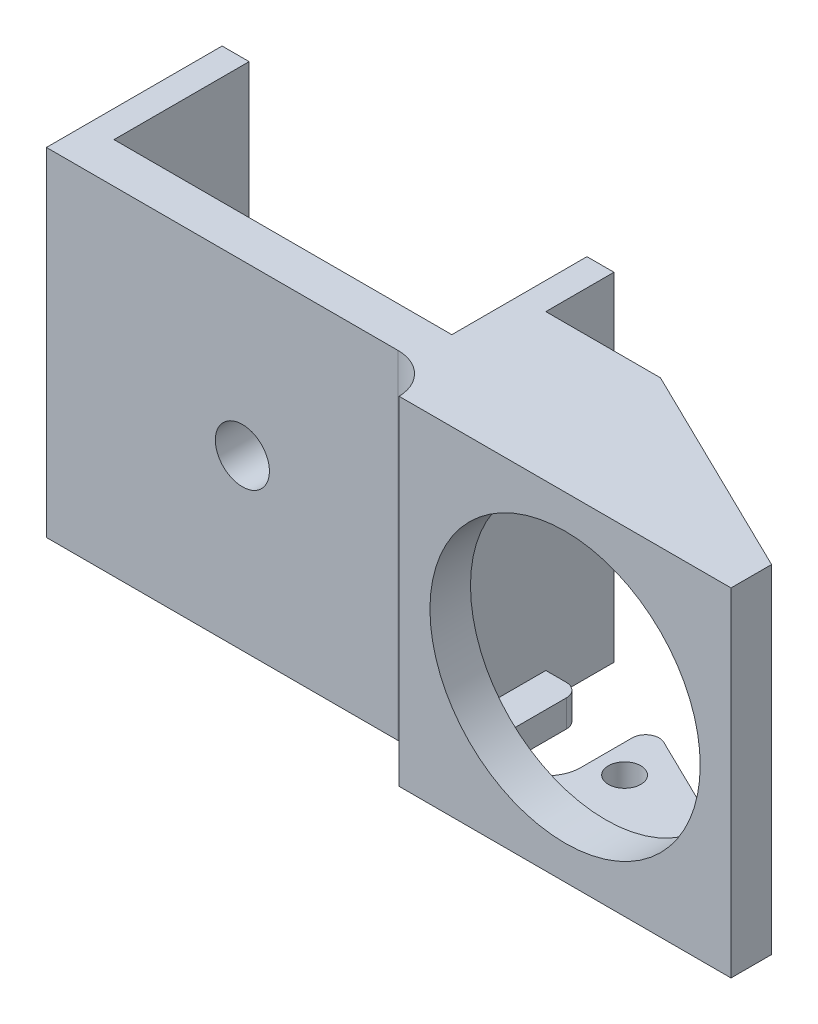
SolidWorks part; units mm, degrees
ref_plane "Front" through (0, 0, 0) normal (0, 0, 1) x (1, 0, 0)
ref_plane "Top" through (0, 0, 0) normal (0, 1, 0) x (1, 0, 0)
ref_plane "Right" through (0, 0, 0) normal (1, 0, 0) x (0, 0, -1)
sketch "Эскиз1" plane through (0, 0, 0) normal (0, 0, 1) x (1, 0, 0)
  line L1 (-12.2807, 12.5) -> (12.2807, 12.5)
  line L2 (-12.2807, 12.5) -> (-12.2807, -12.5)
  line L3 (-12.2807, -12.5) -> (12.2807, -12.5)
  line L4 (12.2807, 12.5) -> (12.2807, -12.5)
  line L5 (-12.2807, 12.5) -> (12.2807, -12.5) construction
  line L6 (-12.2807, -12.5) -> (12.2807, 12.5) construction
  circle A0 centre (0, 0) radius 10
  dimension "D1" = 25
  dimension "D2" = 20
extrude "Бобышка-Вытянуть1" add sketch "Эскиз1" along normal blind 3
sketch "Эскиз2" plane through (0, 0, 3) normal (0, 0, 1) x (1, 0, 0)
  line L0 (-12.2807, 12.5) -> (-41.2807, 12.5)
  line L1 (-41.2807, 12.5) -> (-41.2807, -12.5)
  line L2 (-41.2807, -12.5) -> (-12.2807, -12.5)
  line L3 (-12.2807, 12.5) -> (-12.2807, -12.5)
  dimension "D1" = 29
extrude "Бобышка-Вытянуть2" add sketch "Эскиз2" against normal blind 3 from offset 2.9 offset against normal yes
sketch "Эскиз4" plane through (0, 0, -2.9) normal (0, 0, -1) x (-1, 0, 0)
  line L0 (41.2807, -12.5) -> (12.2807, -12.5) construction
  line L1 (12.2807, 12.5) -> (14.2807, 12.5)
  line L2 (12.2807, 12.5) -> (12.2807, -12.5)
  line L3 (12.2807, -12.5) -> (14.2807, -12.5)
  line L4 (14.2807, 12.5) -> (14.2807, -12.5)
  line L6 (41.2807, 12.5) -> (39.2807, 12.5)
  line L7 (41.2807, 12.5) -> (41.2807, -12.5)
  line L8 (41.2807, -12.5) -> (39.2807, -12.5)
  line L9 (39.2807, 12.5) -> (39.2807, -12.5)
  point P12 (0, 0)
  point P13 (0, 0)
  dimension "D1" = 2
  dimension "D2" = 2
extrude "Бобышка-Вытянуть3" add sketch "Эскиз4" along normal blind 10
sketch "Эскиз5" plane through (0, 12.5, 0) normal (0, 1, 0) x (1, 0, 0)
  line L0 (-14.2807, 7.8551) -> (-14.2807, -0.1)
  line L2 (-12.2807, -3) -> (12.2807, -3)
  line L3 (12.2807, -3) -> (12.2807, 0)
  line L4 (12.2807, 0) -> (-3.797, 7.8551)
  line L5 (-3.797, 7.8551) -> (-14.2807, 7.8551)
  line L6 (-14.2807, -0.1) -> (-12.2807, -0.1)
  line L7 (-12.2807, -0.1) -> (-41.2807, -0.1) construction
  line L8 (-12.2807, -0.1) -> (-12.2807, -3)
extrude "Бобышка-Вытянуть4" add sketch "Эскиз5" against normal blind 2
sketch "Эскиз6" plane through (0, -12.5, 0) normal (0, -1, 0) x (1, 0, 0)
  line L0 (-14.2807, -7.8551) -> (-14.2807, 0.1)
  line L2 (-12.2807, 3) -> (12.2807, 3)
  line L3 (12.2807, 3) -> (12.2807, 0)
  line L4 (12.2807, 0) -> (-3.3263, -7.6252)
  line L5 (-10.7653, -7.8551) -> (-14.2807, -7.8551)
  line L6 (-9.7653, -2.9163) -> (-9.7653, -6.8551)
  line L7 (-4.7653, -2.9163) -> (-4.7653, -6.7267)
  line L8 (-3.797, -7.8551) -> (-12.2807, -7.8551) construction
  line L9 (-12.2807, 3) -> (-12.2807, 0.1)
  line L10 (-12.2807, 0.1) -> (-14.2807, 0.1)
  line L11 (-41.2807, 0.1) -> (-12.2807, 0.1) construction
  circle A0 centre (-7.2653, -2.9163) radius 2.5
  arc A1 (-3.3263, -7.6252) -> (-4.7653, -6.7267) centre (-3.7653, -6.7267) cw
  arc A2 (-10.7653, -7.8551) -> (-9.7653, -6.8551) centre (-10.7653, -6.8551) ccw
  circle A3 centre (-2.6633, -4.067) radius 1.2
  point P1 (-9.7653, -7.8551)
  point P20 (-9.7653, -7.8551)
  point P21 (-9.7653, -10.7711)
  dimension "D1" = 1
  dimension "D2" = 1
extrude "Бобышка-Вытянуть5" add sketch "Эскиз6" against normal blind 2
sketch "Эскиз7" plane through (0, 0, -2.9) normal (0, 0, -1) x (-1, 0, 0)
  circle A0 centre (26.7807, 0) radius 2
  point P2 (0, 0)
extrude "Вырез-Вытянуть1" cut sketch "Эскиз7" against normal through all
fillet "Скругление1" radius 3 1 edges at (-12.2807, 0, 0.1)
